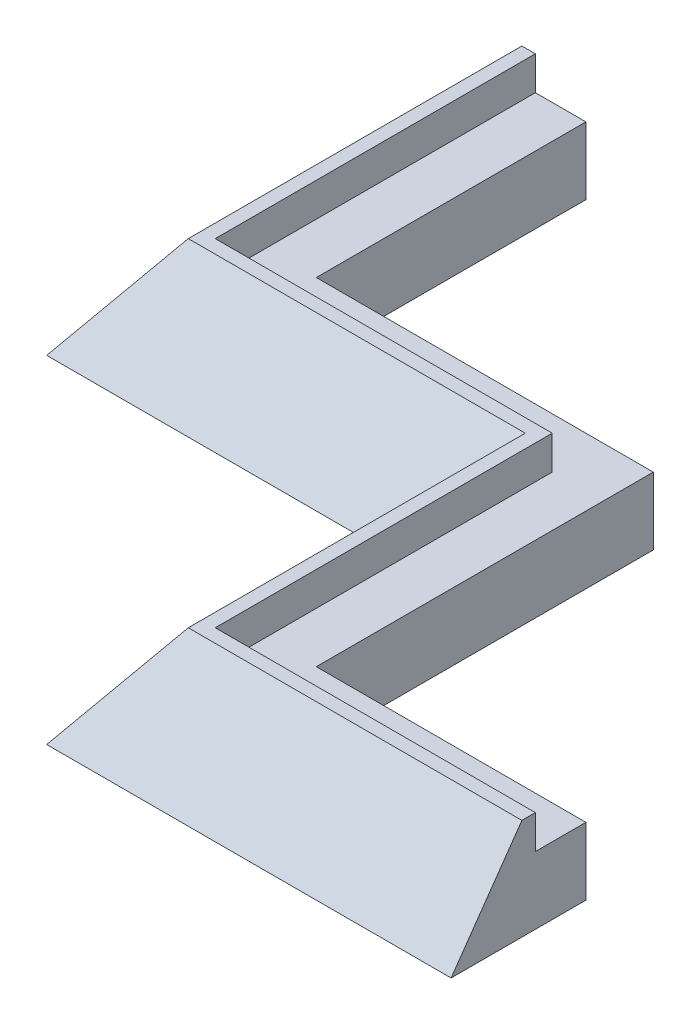
SolidWorks part; units mm, degrees
ref_plane "Plan de face" through (0, 0, 0) normal (0, 0, 1) x (1, 0, 0)
ref_plane "Plan de dessus" through (0, 0, 0) normal (0, 1, 0) x (1, 0, 0)
ref_plane "Plan de droite" through (0, 0, 0) normal (1, 0, 0) x (0, 0, -1)
sketch "Esquisse1" plane through (0, 0, 0) normal (0, 1, 0) x (1, 0, 0)
  line L0 (-41.3523, -18.6477) -> (8.6477, -18.6477)
  line L1 (68.6477, -68.6477) -> (8.6477, -68.6477)
  line L2 (68.6477, -68.6477) -> (68.6477, -48.6477)
  line L3 (-21.3523, 41.3523) -> (-41.3523, 41.3523)
  line L4 (-41.3523, -18.6477) -> (-41.3523, 41.3523)
  line L5 (68.6477, -68.6477) -> (-41.3523, 41.3523) construction
  line L6 (55, 80) -> (-55, -80) construction
  line L7 (8.6477, -18.6477) -> (8.6477, -68.6477)
  line L8 (-21.3523, 41.3523) -> (-21.3523, 1.3523)
  line L9 (-21.3523, 1.3523) -> (28.6477, 1.3523)
  line L10 (28.6477, 1.3523) -> (28.6477, -48.6477)
  line L11 (28.6477, -48.6477) -> (68.6477, -48.6477)
  point P0 (0, 0)
  dimension "D1" = 110
  dimension "D2" = 110
  dimension "D3" = 50
  dimension "D4" = 20
  dimension "D5" = 20
  dimension "D6" = 20
  dimension "D7" = 20
extrude "Boss.-Extru.1" add sketch "Esquisse1" along normal blind 15
chamfer "Chanfrein1" distance 15 angle 35 4 edges at (38.6477, 15, 68.6477) (8.6477, 15, 43.6477) (-16.3523, 15, 18.6477) (-41.3523, 15, -11.3523) first distance on face at (38.6477, 7.5, 68.6477) first distance on face at (8.6477, 7.5, 43.6477) first distance on face at (-16.3523, 7.5, 18.6477) first distance on face at (-41.3523, 7.5, -11.3523)
sketch "Esquisse2" plane through (0, 15, 0) normal (0, 1, 0) x (1, 0, 0)
  line L0 (-28.8492, 41.3523) -> (-28.8492, -8.1445)
  line L1 (-21.3523, 41.3523) -> (-30.8492, 41.3523) construction
  line L2 (-30.8492, -8.1445) -> (19.1508, -8.1445) construction
  line L3 (-30.8492, -6.1445) -> (21.1508, -6.1445)
  line L4 (-30.8492, 41.3523) -> (-30.8492, -8.1445) construction
  line L5 (21.1508, -6.1445) -> (21.1508, -56.1445)
  line L6 (21.1508, -56.1445) -> (68.6477, -56.1445)
  line L7 (68.6477, -58.1445) -> (68.6477, -48.6477) construction
  line L8 (68.6477, -56.1445) -> (68.6477, -48.6477)
  line L9 (68.6477, -48.6477) -> (28.6477, -48.6477)
  line L10 (28.6477, -48.6477) -> (28.6477, 1.3523)
  line L11 (28.6477, 1.3523) -> (-21.3523, 1.3523)
  line L12 (-21.3523, 1.3523) -> (-21.3523, 41.3523)
  line L13 (-21.3523, 41.3523) -> (-28.8492, 41.3523)
  line L14 (19.1508, -8.1445) -> (19.1508, -58.1445) construction
  line L15 (19.1508, -58.1445) -> (68.6477, -58.1445) construction
  line M7 (68.6477, -58.1445) -> (68.6477, -48.6477)
  line M8 (68.6477, -48.6477) -> (28.6477, -48.6477)
  line M9 (28.6477, -48.6477) -> (28.6477, 1.3523)
  line M10 (28.6477, 1.3523) -> (-21.3523, 1.3523)
  line M11 (-21.3523, 1.3523) -> (-21.3523, 41.3523)
  line M12 (-21.3523, 41.3523) -> (-30.8492, 41.3523)
  dimension "D1" = 2
  dimension "D2" = 2
  dimension "D3" = 2
  dimension "D4" = 2
extrude "Enlèv. mat.-Extru.1" cut sketch "Esquisse2" against normal blind 5 contours L5 L6 L0 L3 M7 M8 M9 M10 M11 M12 region at (-25.1008, 15, -39.9735)
